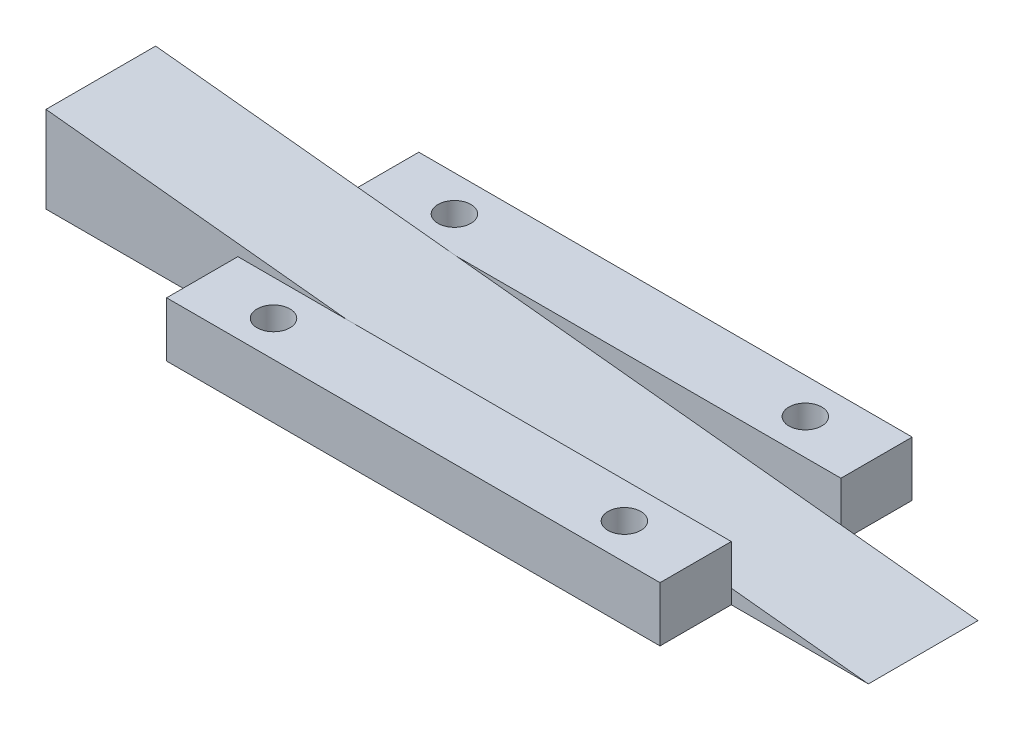
SolidWorks part; units mm, degrees
ref_plane "Front Plane" through (0, 0, 0) normal (0, 0, 1) x (1, 0, 0)
ref_plane "Top Plane" through (0, 0, 0) normal (0, 1, 0) x (1, 0, 0)
ref_plane "Right Plane" through (0, 0, 0) normal (1, 0, 0) x (0, 0, -1)
sketch "Sketch1" plane through (0, 0, 0) normal (0, 0, 1) x (1, 0, 0)
  line L0 (-50.1477, 0) -> (99.8523, 0)
  line L1 (55, 0) -> (-55, 0) construction
  line L2 (99.8523, 0) -> (-50.1477, 15.7656)
  line L3 (-50.1477, 15.7656) -> (-50.1477, 0)
  dimension "D1" = 150
  dimension "D2" = 6
extrude "Boss-Extrude1" add sketch "Sketch1" along normal mid plane 20
sketch "Sketch2" plane through (0, 0, 10) normal (0, 0, 1) x (1, 0, 0)
  line L0 (-15.1477, 0) -> (-15.1477, 10)
  line L1 (-15.1477, 0) -> (74.8523, 0)
  line L2 (-15.1477, 10) -> (74.8523, 10)
  line L3 (74.8523, 0) -> (74.8523, 10)
  line L4 (11, 0) -> (-11, 0) construction
  line L5 (-50.1477, 15.7656) -> (-50.1477, 0) construction
  dimension "D1" = 10
  dimension "D2" = 35
  dimension "D3" = 90
extrude "Boss-Extrude2" add sketch "Sketch2" along normal blind 13
sketch "Sketch3" plane through (0, 0, -10) normal (0, 0, 1) x (1, 0, 0)
  line L0 (-15.1477, 0) -> (-15.1477, 10)
  line L1 (-15.1477, 0) -> (74.8523, 0)
  line L2 (-15.1477, 10) -> (74.8523, 10)
  line L3 (74.8523, 0) -> (74.8523, 10)
  line L6 (-50.1477, 15.7656) -> (-50.1477, 0) construction
  dimension "D1" = 10
  dimension "D2" = 35
  dimension "D3" = 90
extrude "Boss-Extrude3" add sketch "Sketch3" against normal blind 13
sketch "Sketch4" plane through (0, 10, -20) normal (0, -1, 0) x (1, 0, 0)
  line L0 (-15.1477, 43) -> (74.8523, 43) construction
  line L1 (74.8523, -3) -> (74.8523, 10) construction
  line L2 (-15.1477, -3) -> (-15.1477, 10) construction
  line L3 (-15.1477, -3) -> (74.8523, -3) construction
  line L6 (-2.1477, 36.5) -> (61.8523, 36.5) construction
  line L7 (61.8523, 36.5) -> (61.8523, 3.5) construction
  line L8 (61.8523, 3.5) -> (-2.1477, 3.5) construction
  line L9 (-2.1477, 3.5) -> (-2.1477, 36.5) construction
  circle A0 centre (-2.1477, 36.5) radius 3
  circle A1 centre (61.8523, 36.5) radius 3
  circle A2 centre (61.8523, 3.5) radius 3
  circle A3 centre (-2.1477, 3.5) radius 3
  dimension "D1" = 6
  dimension "D2" = 6.5
  dimension "D3" = 13
  dimension "D4" = 13
  dimension "D5" = 6.5
extrude "Cut-Extrude1" cut sketch "Sketch4" along normal blind 13
